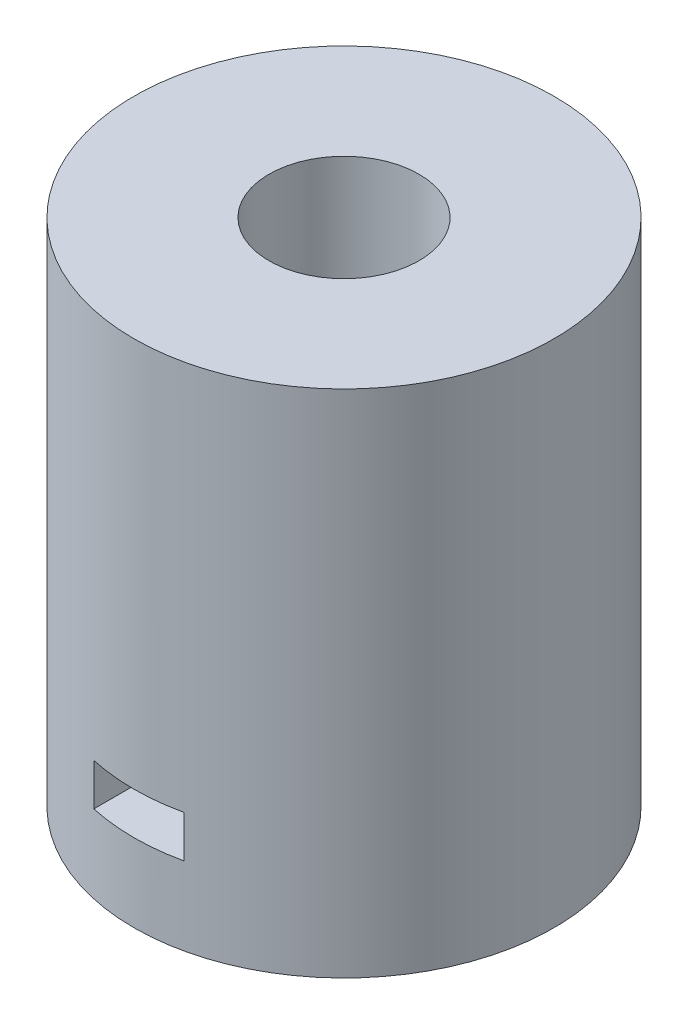
SolidWorks part; units mm, degrees
ref_plane "Front Plane" through (0, 0, 0) normal (0, 0, 1) x (1, 0, 0)
ref_plane "Top Plane" through (0, 0, 0) normal (0, 1, 0) x (1, 0, 0)
ref_plane "Right Plane" through (0, 0, 0) normal (1, 0, 0) x (0, 0, -1)
sketch "Sketch1" plane through (0, 0, 0) normal (0, 1, 0) x (1, 0, 0)
  line L0 (0, 0) -> (0, 15.7593) construction
  line L1 (0, 0) -> (10.6324, 0) construction
  circle A0 centre (0, 0) radius 35
  circle A1 centre (0, 15) radius 3.15
  circle A2 centre (0, -15) radius 3.15
  dimension "D1" = 6.3
  dimension "D2" = 70
  dimension "D3" = 15
extrude "Boss-Extrude1" add sketch "Sketch1" along normal blind 13
sketch "Sketch2" plane through (0, 13, 0) normal (0, 1, 0) x (1, 0, 0)
  line L0 (0, 15) -> (0, 25.687) construction
  line L6 (7.5, 34.187) -> (7.5, 6.5)
  line L7 (7.5, 6.5) -> (-7.5, 6.5)
  line L8 (-7.5, 34.187) -> (-7.5, 6.5)
  line L9 (7.5, 34.187) -> (-7.5, 6.5) construction
  line L10 (7.5, 6.5) -> (-7.5, 34.187) construction
  line L11 (0, 0) -> (5.5829, 0) construction
  line L12 (-7.5, -34.187) -> (-7.5, -6.5)
  line L13 (7.5, -6.5) -> (-7.5, -6.5)
  line L14 (7.5, -34.187) -> (7.5, -6.5)
  arc A0 (7.5, 34.187) -> (-7.5, 34.187) centre (0, 0) ccw
  circle A1 centre (0, 0) radius 35 construction
  circle A2 centre (0, 15) radius 6.7
  circle A3 centre (0, 0) radius 35
  arc A4 (7.5, -34.187) -> (-7.5, -34.187) centre (0, 0) cw
  point P0 (0, 20.3435)
  circle M11 centre (0, 0) radius 35
  circle M12 centre (0, -15) radius 3.15
  dimension "D2" = 13.4
  dimension "D1" = 15
  dimension "D3" = 8.5
extrude "Boss-Extrude2" add sketch "Sketch2" along normal blind 7 contours L8 L6 L7 M11 M12 region at (0, 13, 0)
sketch "Sketch4" plane through (0, 0, 0) normal (0, 0, 1) x (1, 0, 0)
  line L0 (0, 20) -> (35, 20)
  line L2 (0, 0) -> (0, 55.2278) construction
  line L4 (35, 20) -> (7.5, 20) construction
  line L6 (35, 0) -> (35, 20) construction
  line L7 (12.5, 20) -> (12.5, 85)
  line L8 (12.5, 85) -> (35, 85)
  line L9 (35, 85) -> (35, 20)
  dimension "D1" = 12.5
  dimension "D3" = 65
revolve "Revolve1" add sketch "Sketch4" angle 360 about L2 region at (23.75, 52.5, 0)
